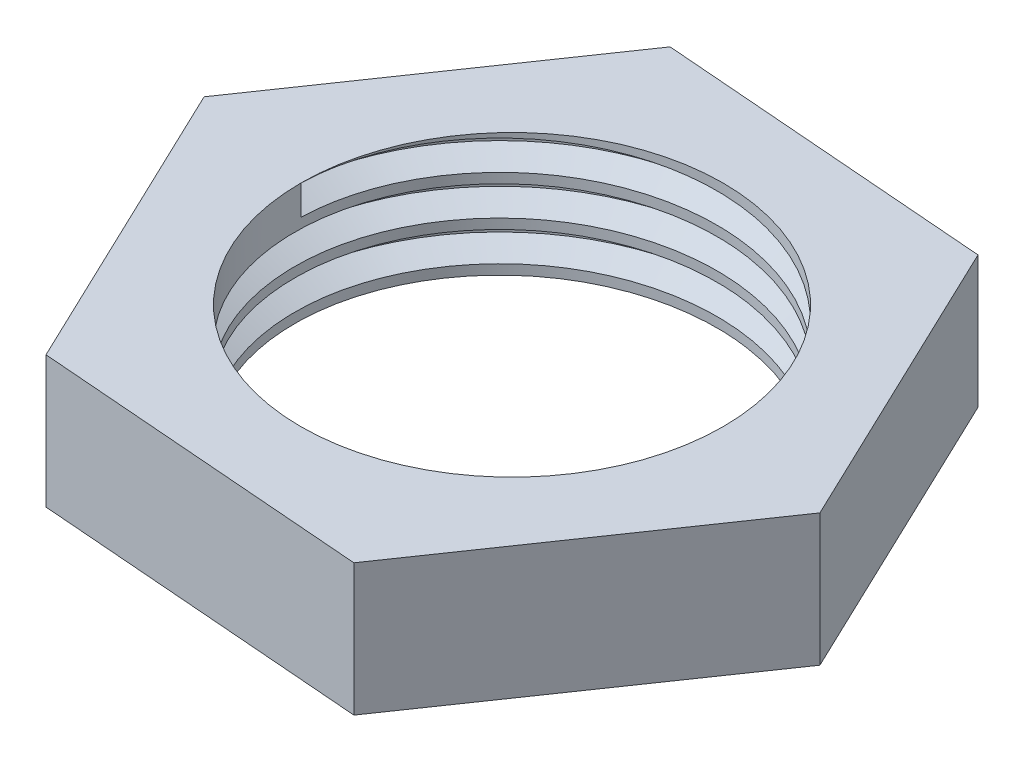
SolidWorks part; units mm, degrees
ref_plane "Front Plane" through (0, 0, 0) normal (0, 0, 1) x (1, 0, 0)
ref_plane "Top Plane" through (0, 0, 0) normal (0, 1, 0) x (1, 0, 0)
ref_plane "Right Plane" through (0, 0, 0) normal (1, 0, 0) x (0, 0, -1)
sketch "Sketch1" plane through (0, 0, 0) normal (0, 1, 0) x (1, 0, 0)
  line L1 (7.1918, 10.4695) -> (-5.471, 11.4631)
  line L2 (-5.471, 11.4631) -> (-12.6628, 0.9935)
  line L3 (-12.6628, 0.9935) -> (-7.1918, -10.4695)
  line L4 (-7.1918, -10.4695) -> (5.471, -11.4631)
  line L5 (5.471, -11.4631) -> (12.6628, -0.9935)
  line L6 (12.6628, -0.9935) -> (7.1918, 10.4695)
  circle A0 centre (0, 0) radius 11 construction
  circle A1 centre (0, 0) radius 8
extrude "Boss-Extrude1" add sketch "Sketch1" along normal blind 5
thread "Thread1" pitch 1.5 method cut profile "Thread Profile1" start angle 0, offset 0, length 5, pitch 1.5, diameter 16
ref_plane "Plane1" through (-8, 5, 0) normal (0, 0, 1) x (-1, 0, 0)
sketch "Thread Profile1" plane through (-8, 5, 0) normal (0, 0, 1) x (-1, 0, 0)
  line L0 (0, 0) -> (0, 1.5) construction
  line L1 (0, 0) -> (0.8119, 0.4687)
  line L2 (0.8119, 0.4687) -> (0.8119, 0.6562)
  line L3 (0.8119, 0.6562) -> (0, 1.125)
  line L4 (0.8119, 0.5625) -> (0, 0.5625) construction
  line L11 (0, 0) -> (0, 1.125)
  point P2 (0, 0)
  dimension "Pitch" = 1.5
  dimension "Profile_Angle" = 60
  dimension "Profile_Land" = 0.1875
  dimension "Profile_Height" = 0.8119
